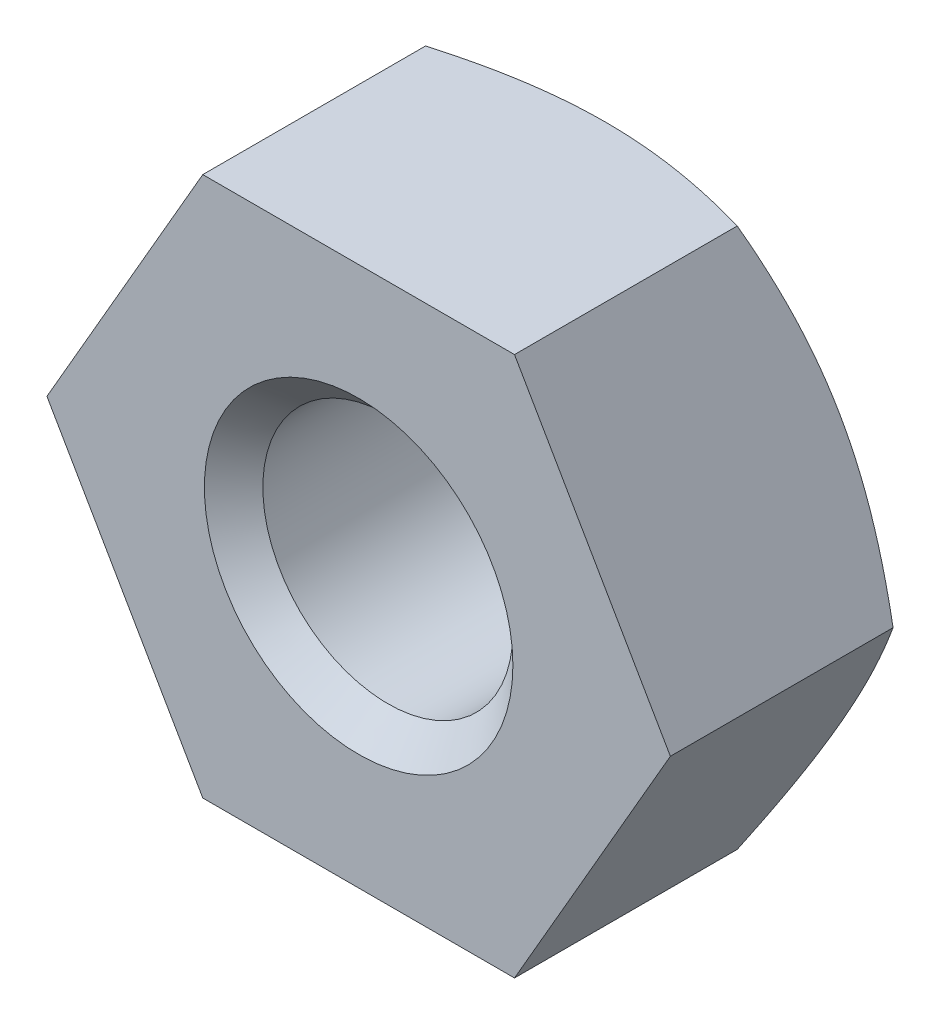
SolidWorks part; units mm, degrees
ref_plane "前视基准面" through (0, 0, 0) normal (0, 0, 1) x (1, 0, 0)
ref_plane "上视基准面" through (0, 0, 0) normal (0, 1, 0) x (1, 0, 0)
ref_plane "右视基准面" through (0, 0, 0) normal (1, 0, 0) x (0, 0, -1)
ref_plane "基准面4" through (0, 0, 0) normal (1, 0, 0) x (0, 0, -1)
sketch "草图1" plane through (0, 0, 0) normal (1, 0, 0) x (0, 0, -1)
  line L0 (0, 0) -> (0, 9.0426)
  line L1 (0, 9.0426) -> (3.2, 3.5)
  line L2 (3.2, 3.5) -> (3.2, 0)
  line L3 (3.2, 0) -> (0, 0)
  line L4 (3.2, 0) -> (0, 0) construction
revolve "旋转1" add sketch "草图1" angle 360 about L4 reverse direction yes
ref_plane "基准面5" through (0, 0, -3.2) normal (0, 0, -1) x (-1, 0, 0)
sketch "草图2" plane through (0, 0, -3.2) normal (0, 0, -1) x (-1, 0, 0)
  line L0 (-2.0207, -3.5) -> (2.0207, -3.5)
  line L1 (2.0207, -3.5) -> (4.0415, 0)
  line L2 (4.0415, 0) -> (2.0207, 3.5)
  line L3 (2.0207, 3.5) -> (-2.0207, 3.5)
  line L4 (-2.0207, 3.5) -> (-4.0415, 0)
  line L5 (-4.0415, 0) -> (-2.0207, -3.5)
  circle A0 centre (0, 0) radius 14
extrude "切除-拉伸1" cut sketch "草图2" against normal blind 3.2
sketch "草图3" plane through (0, 0, 0) normal (1, 0, 0) x (0, 0, -1)
  line L0 (0, 0) -> (0, 2)
  line L1 (0, 2) -> (0.379, 1.621)
  line L2 (0.379, 1.621) -> (2.821, 1.621)
  line L3 (2.821, 1.621) -> (3.2, 2)
  line L4 (3.2, 2) -> (3.2, 0)
  line L5 (3.2, 0) -> (0, 0)
  line L6 (3.2, 0) -> (0, 0) construction
revolve "切除-旋转1" cut sketch "草图3" angle 360 about L6 reverse direction yes
cosmetic thread "装饰螺纹线1" parameters "D1"=3.2, "D2"=4
ref_plane "基准面6" through (0, 0, 0) normal (0, 0, 1) x (1, 0, 0)
ref_plane "to_motor XY" through (0, 0, 0) normal (0, 0, 1) x (1, 0, 0)
ref_plane "to_motor XZ" through (0, 0, 0) normal (0, -1, 0) x (-1, 0, 0)
ref_plane "to_motor YZ" through (0, 0, 0) normal (1, 0, 0) x (0, 0, -1)
ref_axis "to_motor X" through (-80.9, 0, 0) along (1, 0, 0)
ref_axis "to_motor Y" through (0, -50, 0) along (0, 1, 0)
ref_axis "to_motor Z" through (0, 0, 80.9) along (0, 0, -1)
sketch3d "to_motor"
  point P0 (0, 0, 0)
